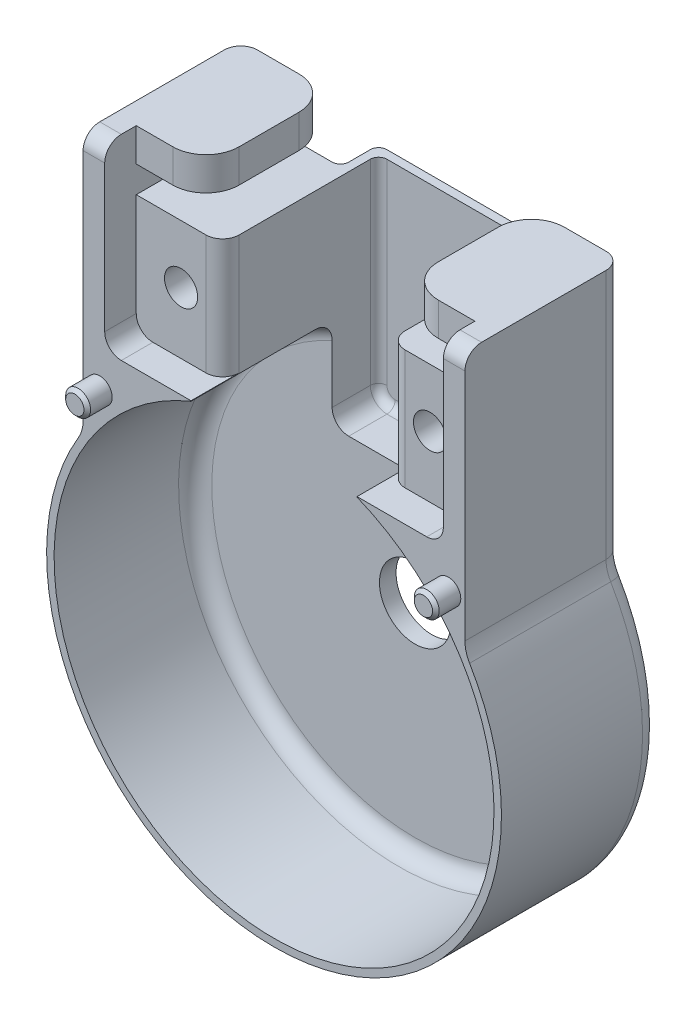
SolidWorks part; units mm, degrees
material "ABS PC"
ref_plane "前视基准面" through (0, 0, 0) normal (0, 0, 1) x (1, 0, 0)
ref_plane "上视基准面" through (0, 0, 0) normal (0, 1, 0) x (1, 0, 0)
ref_plane "右视基准面" through (0, 0, 0) normal (1, 0, 0) x (0, 0, -1)
sketch "草图1" plane through (0, 0, 0) normal (0, 0, 1) x (1, 0, 0)
  line L0 (-13.7, 0) -> (-13.7, 19.5)
  line L1 (-13.7, 19.5) -> (13.7, 19.5)
  line L2 (13.7, 19.5) -> (13.7, 0)
  circle A0 centre (0, 0) radius 13.7 construction
  arc A1 (-13.7, 0) -> (13.7, 0) centre (0, 0) ccw
  dimension "D1" = 27.4
  dimension "D2" = 19.5
extrude "凸台-拉伸1" add sketch "草图1" along normal blind 9.5
sketch "草图2" plane through (0, 0, 9.5) normal (0, 0, 1) x (1, 0, 0)
  circle A0 centre (0, 0) radius 13.25
  dimension "D1" = 26.5
extrude "切除-拉伸1" cut sketch "草图2" against normal offset from surface (8.5 mm away) 1 up to face at (0, 6.325, 0)
sketch "草图3" plane through (0, 0, 9.5) normal (0, 0, 1) x (1, 0, 0)
  line L0 (13.7, 19.5) -> (-13.7, 19.5) construction
  line L1 (5, 32.3) -> (-5, 32.3)
  line L2 (5, 32.3) -> (5, 6.7)
  line L3 (5, 6.7) -> (-5, 6.7)
  line L4 (-5, 32.3) -> (-5, 6.7)
  line L5 (5, 32.3) -> (-5, 6.7) construction
  line L6 (5, 6.7) -> (-5, 32.3) construction
  point P0 (0, 19.5)
  dimension "D1" = 10
  dimension "D2" = 12.8
extrude "切除-拉伸2" cut sketch "草图3" against normal blind 27
sketch "草图8" plane through (0, 0, 1) normal (0, 0, 1) x (1, 0, 0)
  circle A0 centre (0, 0) radius 2.15
  dimension "D1" = 4.3
extrude "切除-拉伸5" cut sketch "草图8" against normal blind 10
sketch "草图9" plane through (0, 0, 9.5) normal (0, 0, 1) x (1, 0, 0)
  line L0 (0, 0) -> (0, 26.9482) construction
  line L2 (10.2, 26.2414) -> (-10.2, 26.2414)
  line L3 (10.2, 26.2414) -> (10.2, 12.3)
  line L4 (10.2, 12.3) -> (-10.2, 12.3)
  line L5 (-10.2, 26.2414) -> (-10.2, 12.3)
  line L6 (10.2, 26.2414) -> (-10.2, 12.3) construction
  line L7 (10.2, 12.3) -> (-10.2, 26.2414) construction
  line L8 (-5, 19.5) -> (-13.7, 19.5) construction
  point P3 (0, 19.2707)
  dimension "D1" = 7.2
  dimension "D2" = 20.4
extrude "切除-拉伸6" cut sketch "草图9" against normal blind 1.9
sketch "草图10" plane through (0, 0, 0) normal (0, 0, -1) x (-1, 0, 0)
  line L0 (-13.7, 19.5) -> (-5, 19.5) construction
  line L1 (7.5, -16) -> (-7.5, -16) construction
  line L2 (7.5, -16) -> (7.5, 16) construction
  line L3 (7.5, 16) -> (-7.5, 16) construction
  line L4 (-7.5, -16) -> (-7.5, 16) construction
  line L5 (7.5, -16) -> (-7.5, 16) construction
  line L6 (7.5, 16) -> (-7.5, -16) construction
  circle A0 centre (-7.5, 16) radius 2
  circle A1 centre (7.5, 16) radius 2
  point P0 (0, 0)
  dimension "D3" = 4
  dimension "D4" = 4
  dimension "D1" = 15
  dimension "D2" = 3.5
extrude "切除-拉伸7" cut sketch "草图10" against normal offset from surface (5.6 mm away) 2 up to face at (7.6, 15.9, 7.6)
fillet "圆角8" radius 1 2 edges at (10.2, 12.3, 8.55) (-10.2, 12.3, 8.55)
sketch "草图17" plane through (0, 19.5, 0) normal (0, 1, 0) x (1, 0, 0)
  line L0 (0, 3.35) -> (0, -13.0876) construction
  line L1 (5, -7.6) -> (5, 0)
  line L2 (10.2, -7.6) -> (5, -7.6)
  line L3 (10.2, -9.5) -> (10.2, -7.6)
  line L4 (13.7, -9.5) -> (10.2, -9.5)
  line L5 (13.7, 0) -> (13.7, -9.5)
  line L6 (-5, 0) -> (-13.7, 0)
  line L7 (-5, 0) -> (-13.7, 0)
  line L8 (5, 0) -> (13.7, 0)
  line L13 (-13.7, 0) -> (-13.7, -9.5)
  line L14 (-13.7, -9.5) -> (-10.2, -9.5)
  line L15 (-10.2, -9.5) -> (-10.2, -7.6)
  line L16 (-10.2, -7.6) -> (-5, -7.6)
  line L17 (-5, -7.6) -> (-5, 0)
  line L25 (-13.7, 0) -> (-13.7, -9.5)
  line L26 (-13.7, -9.5) -> (-10.2, -9.5)
  line L27 (-10.2, -9.5) -> (-10.2, -7.6)
  line L28 (-10.2, -7.6) -> (-5, -7.6)
  line L29 (-5, -7.6) -> (-5, 0)
  dimension "D1" = 0
extrude "凸台-拉伸4" add sketch "草图17" along normal blind 3.6
sketch "草图18" plane through (0, 0, 9.5) normal (0, 0, 1) x (1, 0, 0)
  line L3 (10.2, 19.5) -> (-10.2, 19.5)
  line L4 (10.2, 19.5) -> (10.2, 21.1)
  line L5 (10.2, 21.1) -> (-10.2, 21.1)
  line L6 (-10.2, 19.5) -> (-10.2, 21.1)
  line L7 (10.2, 19.5) -> (-10.2, 21.1) construction
  line L8 (10.2, 21.1) -> (-10.2, 19.5) construction
  line L9 (-10.2, 23.1) -> (-10.2, 13.3) construction
  dimension "D1" = 19.5
  dimension "D2" = 1.6
  dimension "D3" = 20.4
extrude "切除-拉伸10" cut sketch "草图18" against normal blind 23.6
sketch "草图21" plane through (0, 0, 9.5) normal (0, 0, 1) x (1, 0, 0)
  line L1 (-5, 19.5) -> (-10.2, 19.5) construction
  line L2 (-5, 19.5) -> (-5, 12.3) construction
  circle A0 centre (-10.5, 10.1) radius 0.75
  dimension "D1" = 5.5
  dimension "D2" = 9.4
  dimension "D3" = 1.5
extrude "凸台-拉伸6" add sketch "草图21" along normal blind 1.5
mirror "镜向1" about plane through (0, 0, 0) normal (1, 0, 0) of "凸台-拉伸6"
chamfer "倒角3" distance 0.2 angle 45 2 edges at (9.75, 10.1, 11) (-9.75, 10.1, 11)
sketch "草图22" plane through (0, 23.1, 0) normal (0, 1, 0) x (1, 0, 0)
  line L1 (6, 13.3591) -> (-6, 13.3591)
  line L2 (6, 13.3591) -> (6, -13.3591)
  line L3 (6, -13.3591) -> (-6, -13.3591)
  line L4 (-6, 13.3591) -> (-6, -13.3591)
  line L5 (6, 13.3591) -> (-6, -13.3591) construction
  line L6 (6, -13.3591) -> (-6, 13.3591) construction
  point P0 (0, 0)
  dimension "D1" = 12
extrude "切除-拉伸12" cut sketch "草图22" against normal up to surface (2 mm away) up to face at (-7.6, 21.1, 3.8)
fillet "圆角9" radius 2 4 edges at (-6, 22.1, 0) (-6, 22.1, 7.6) (6, 22.1, 0) (6, 22.1, 7.6)
sketch "草图23" plane through (0, 0, 0) normal (0, 0, -1) x (-1, 0, 0)
  line L0 (-11.5, 26.537) -> (-11.5, 7.4458)
  line L4 (-11.5, 26.537) -> (-15.4065, 26.537)
  line L5 (-13.7, 0) -> (-15.4065, 0)
  line L6 (-15.4065, 0) -> (-15.4065, 26.537)
  arc A0 (-13.7, 0) -> (-11.5, 7.4458) centre (0, 0) cw
  circle A1 centre (-7.5, 16) radius 2 construction
  dimension "D1" = 4
  dimension "D2" = 13.7
extrude "切除-拉伸13" cut sketch "草图23" against normal blind 27
mirror "镜向2" about plane through (0, 0, 0) normal (1, 0, 0) of "切除-拉伸13"
sketch "草图24" plane through (0, 0, 0) normal (0, 0, -1) x (-1, 0, 0)
  line L0 (-5.5, 19.5) -> (-5.5, 6.2)
  line L1 (-5, 19.5) -> (5, 19.5) construction
  line L2 (-5, 19.5) -> (-5, 6.7)
  line L3 (-5, 6.7) -> (5, 6.7)
  line L4 (5, 19.5) -> (5, 6.7)
  line L5 (-5.5, 19.5) -> (5.5, 19.5) construction
  line L6 (5.5, 19.5) -> (5.5, 6.2)
  line L7 (-5.5, 6.2) -> (5.5, 6.2)
  line L11 (-5, 19.5) -> (-5.5, 19.5)
  line L12 (5, 19.5) -> (5.5, 19.5)
  line L13 (-5, 19.5) -> (-10.2, 19.5) construction
  line L14 (-5, 6.7) -> (-5, 19.5) construction
  dimension "D1" = 0.5
  dimension "D2" = 0.5
extrude "凸台-拉伸7" add sketch "草图24" along normal blind 1.8
sketch "草图25" plane through (0, 0, -1.8) normal (0, 0, -1) x (-1, 0, 0)
  line L1 (-5.5, 19.5) -> (5.5, 19.5)
  line L2 (-5.5, 19.5) -> (-5.5, 6.2)
  line L3 (-5.5, 6.2) -> (5.5, 6.2)
  line L4 (5.5, 19.5) -> (5.5, 6.2)
extrude "凸台-拉伸8" add sketch "草图25" along normal blind 0.5
fillet "圆角10" radius 1 4 edges at (5, 6.7, -0.4) (-5, 6.7, -0.4) (-5.5, 6.2, -1.15) (5.5, 6.2, -1.15)
sketch "草图27" plane through (0, 0, 9.5) normal (0, 0, 1) x (1, 0, 0)
  line L0 (0, 0) -> (0, 32.1569) construction
  line L2 (9.2, 37.7371) -> (-9.2, 37.7371)
  line L3 (9.2, 37.7371) -> (9.2, 5.5601)
  line L4 (9.2, 5.5601) -> (-9.2, 5.5601)
  line L5 (-9.2, 37.7371) -> (-9.2, 5.5601)
  line L6 (9.2, 37.7371) -> (-9.2, 5.5601) construction
  line L7 (9.2, 5.5601) -> (-9.2, 37.7371) construction
  point P2 (0, 21.6486)
  dimension "D1" = 18.4
extrude "切除-拉伸14" [suppressed] cut sketch "草图27" against normal up to surface (1.9 mm away) up to face at (-7.9614, 15.3386, 7.6)
fillet "圆角11" radius 2 2 edges at (11.5, 7.4458, 4.75) (-11.5, 7.4458, 4.75)
fillet "圆角12" radius 1 6 edges at (-11.5, 15.5575, 0) (-11.5713, 7.4856, 0) (0, -13.7, 0) (11.5713, 7.4856, 0) (0, -13.25, 1) (11.5, 15.5575, 0)
fillet "圆角13" radius 1 2 edges at (5, 15.9, 7.6) (-5, 15.9, 7.6)
fillet "圆角14" radius 0.5 12 edges at (0, 6.2, 0) (5.5, 17.75, 0) (5.5, 11.6, 0) (-5.5, 17.75, 0) (-5.5, 11.6, 0) (-5.2071, 6.4929, -2.3) (5.2071, 6.4929, -2.3) (-5.2071, 6.4929, 0) (5.2071, 6.4929, 0) (5.5, 13.35, -2.3) (-5.5, 13.35, -2.3) (0, 6.2, -2.3)
fillet "圆角15" radius 0.5 5 edges at (4.7071, 6.9929, -1.8) (0, 6.7, -1.8) (-4.7071, 6.9929, -1.8)
fillet "圆角16" radius 1 2 edges at (10.85, 23.1, 9.5) (-10.85, 23.1, 9.5)
sketch "草图28" plane through (0, 0, 5.6) normal (0, 0, -1) x (-1, 0, 0)
  circle A0 centre (-7.5, 16) radius 1
  circle A1 centre (7.5, 16) radius 1
  dimension "D1" = 2
  dimension "D2" = 2
extrude "切除-拉伸15" cut sketch "草图28" against normal blind 10
